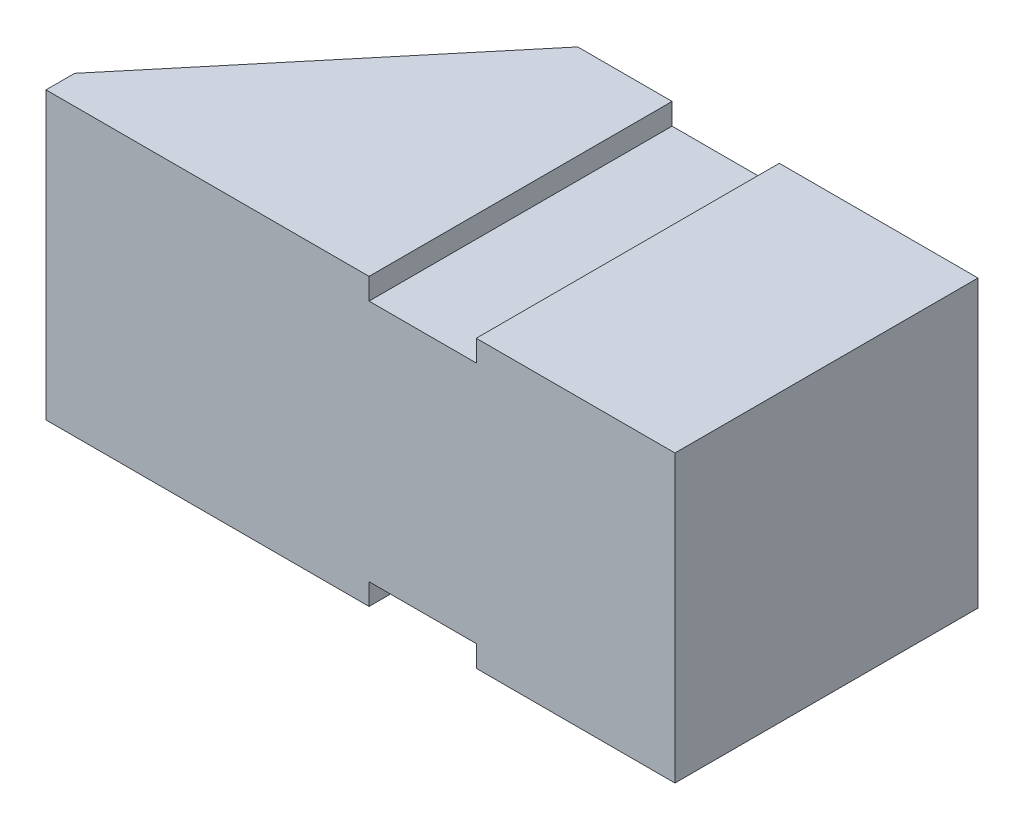
SolidWorks part; units mm, degrees
ref_plane "Front Plane" through (0, 0, 0) normal (0, 0, 1) x (1, 0, 0)
ref_plane "Top Plane" through (0, 0, 0) normal (0, 1, 0) x (1, 0, 0)
ref_plane "Right Plane" through (0, 0, 0) normal (1, 0, 0) x (0, 0, -1)
sketch "Sketch1" plane through (0, 0, 0) normal (0, 0, 1) x (1, 0, 0)
  line L5 (-22, -10) -> (22, -10)
  line L6 (-22, -10) -> (-22, 10)
  line L7 (-22, 10) -> (22, 10)
  line L8 (22, -10) -> (22, 10)
  line L9 (0, 10) -> (0, -10) construction
  line L10 (-22, 0) -> (22, 0) construction
  point P0 (0, 0)
  dimension "D1" = 20
  dimension "D2" = 44
extrude "Boss-Extrude1" add sketch "Sketch1" along normal blind 21.2
sketch "Sketch2" plane through (0, -10, 11.2) normal (0, 1, 0) x (1, 0, 0)
  line L0 (-22, -8) -> (-6, -8) construction
  line L3 (-22, -10) -> (-22, 11.2) construction
  line L5 (-22, -8) -> (-6, 11.2)
  line L6 (22, 11.2) -> (-22, 11.2) construction
  dimension "D1" = 2
  dimension "D2" = 16
extrude "Cut-Extrude1" cut sketch "Sketch2" against normal through all both and the other way through all
sketch "Sketch4" plane through (-3.541, 0, -2.9508) normal (-0.7682, 0, -0.6402) x (-0.6402, 0, 0.7682)
  line L0 (28.8339, 10) -> (3.8411, 10) construction
  line L1 (6.3411, -7.5) -> (23.3411, -7.5)
  line L2 (6.3411, -7.5) -> (6.3411, 7.5)
  line L3 (6.3411, 7.5) -> (23.3411, 7.5)
  line L4 (23.3411, -7.5) -> (23.3411, 7.5)
  line L5 (3.8411, -10) -> (28.8339, -10) construction
  line L6 (3.8411, -10) -> (3.8411, 10) construction
  dimension "D1" = 17
  dimension "D2" = 2.5
  dimension "D3" = 2.5
  dimension "D4" = 2.5
extrude "Cut-Extrude3" cut sketch "Sketch4" against normal blind 0.7
chamfer "Chamfer3" distance 0.7 angle 45 3 edges at (-13.042, 7.5, 8.4504) (-13.042, -7.5, 8.4504) (-7.6005, 0, 1.9206)
chamfer "Chamfer4" distance 0.7 angle 45 1 edges at (-17.9458, 0, 15.4284)
sketch "Sketch5" plane through (0, 0, 0) normal (0, 0, -1) x (-1, 0, 0)
  line L0 (-22, -10) -> (-22, 10) construction
  line L1 (-8.1, -8.5) -> (-0.6, -8.5)
  line L2 (-8.1, -8.5) -> (-8.1, 8.5)
  line L3 (-8.1, 8.5) -> (-0.6, 8.5)
  line L4 (-0.6, -8.5) -> (-0.6, 8.5)
  line L5 (6, -10) -> (-22, -10) construction
  line L6 (-8.1, -8.5) -> (-8.1, -10.0033)
  line L7 (-8.1, -10.0033) -> (-0.6, -10)
  line L8 (-0.6, -10) -> (-0.6, -8.5)
  line L9 (-8.1, 0) -> (-22, 0) construction
  line L10 (-0.6, 10) -> (-0.6, 8.5)
  line L11 (-8.1, 10.0033) -> (-0.6, 10)
  line L12 (-8.1, 8.5) -> (-8.1, 10.0033)
  point P4 (-22, 0)
  point P5 (-8, -10)
  point P8 (-8.1, 0)
  point P12 (-4.35, -8.5)
  line M5 (-22, -10) -> (6, -10)
  line M7 (6, 10) -> (-22, 10)
  dimension "D1" = 17
  dimension "D2" = 7.5
  dimension "D3" = 13.9
extrude "Cut-Extrude4" cut sketch "Sketch5" against normal through all contours L12 L3 L10 M7 | L8 L1 L6 M5 region at (4.35, -9.25, 0) region at (4.35, 9.25, 0)
